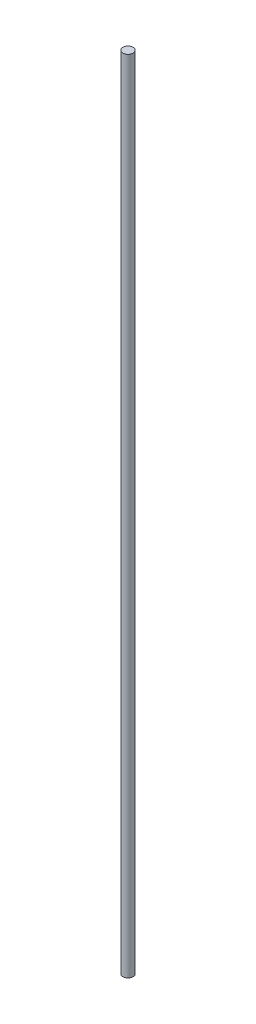
SolidWorks part; units mm, degrees
ref_plane "Front Plane" through (0, 0, 0) normal (0, 0, 1) x (1, 0, 0)
ref_plane "Top Plane" through (0, 0, 0) normal (0, 1, 0) x (1, 0, 0)
ref_plane "Right Plane" through (0, 0, 0) normal (1, 0, 0) x (0, 0, -1)
sketch "Sketch1" plane through (0, 0, 0) normal (0, 1, 0) x (1, 0, 0)
  circle A0 centre (0, 0) radius 1.5
  dimension "D1" = 3
extrude "Boss-Extrude1" add sketch "Sketch1" along normal blind 235
